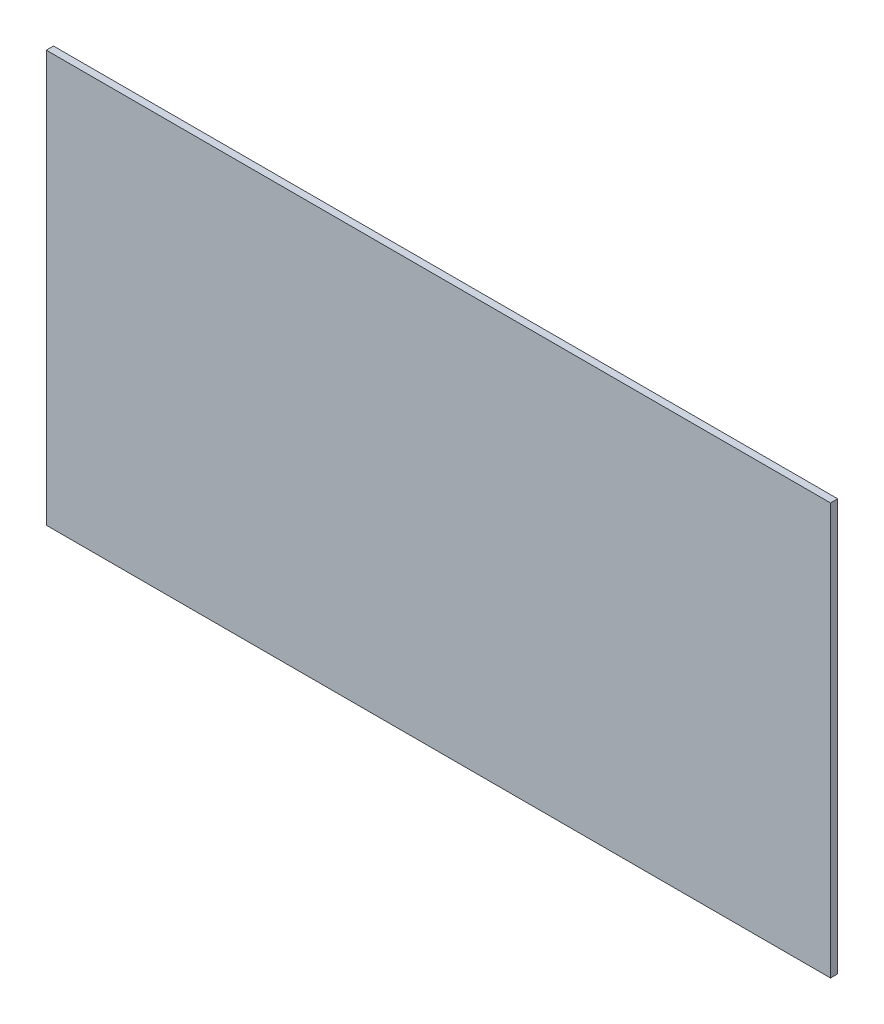
SolidWorks part; units mm, degrees
material "ABS"
ref_plane "X-Y Datum" through (0, 0, 0) normal (0, 0, 1) x (1, 0, 0)
ref_plane "X-Z Datum" through (0, 0, 0) normal (0, 1, 0) x (1, 0, 0)
ref_plane "Y-Z Datum" through (0, 0, 0) normal (1, 0, 0) x (0, 0, -1)
sketch "Sketch1" plane through (0, 0, 0) normal (0, 0, 1) x (1, 0, 0)
  line L0 (-173.025, 90.775) -> (-173.025, -90.775)
  line L1 (-173.025, 90.775) -> (173.025, 90.775)
  line L2 (-173.025, 90.775) -> (-173.025, -90.775)
  line L3 (-173.025, -90.775) -> (173.025, -90.775)
  line L4 (173.025, 90.775) -> (173.025, -90.775)
  line L5 (-173.025, 90.775) -> (173.025, -90.775) construction
  line L6 (-173.025, -90.775) -> (173.025, 90.775) construction
  line L7 (-173.025, -90.775) -> (173.025, -90.775)
  line L8 (173.025, 90.775) -> (173.025, -90.775)
  line L9 (-173.025, 90.775) -> (173.025, 90.775)
  circle A0 centre (-162.25, -80) radius 10.775
  circle A1 centre (-138.25, -80) radius 10.775 construction
  circle A2 centre (-150.25, -57) radius 10.775
  point P0 (0, 0)
  dimension "D1" = 21.55
  dimension "D2" = 24
  dimension "D3" = 23
  dimension "D4" = 12
  dimension "D5" = 181.55
  dimension "D6" = 346.05
  dimension "D7" = 0
extrude "Boss-Extrude1" add sketch "Sketch1" along normal blind 3.175 contours A0 L3 L4 L1 L2 A2 | A2 | A0 | A0 L2 L3 | L9 L0 L7 L8 L1 L4 L3 L2 region at (1.9048, 0.8405, 0) region at (-170.6182, -88.3682, 0) region at (-162.25, -80, 0) region at (-150.25, -57, 0)
